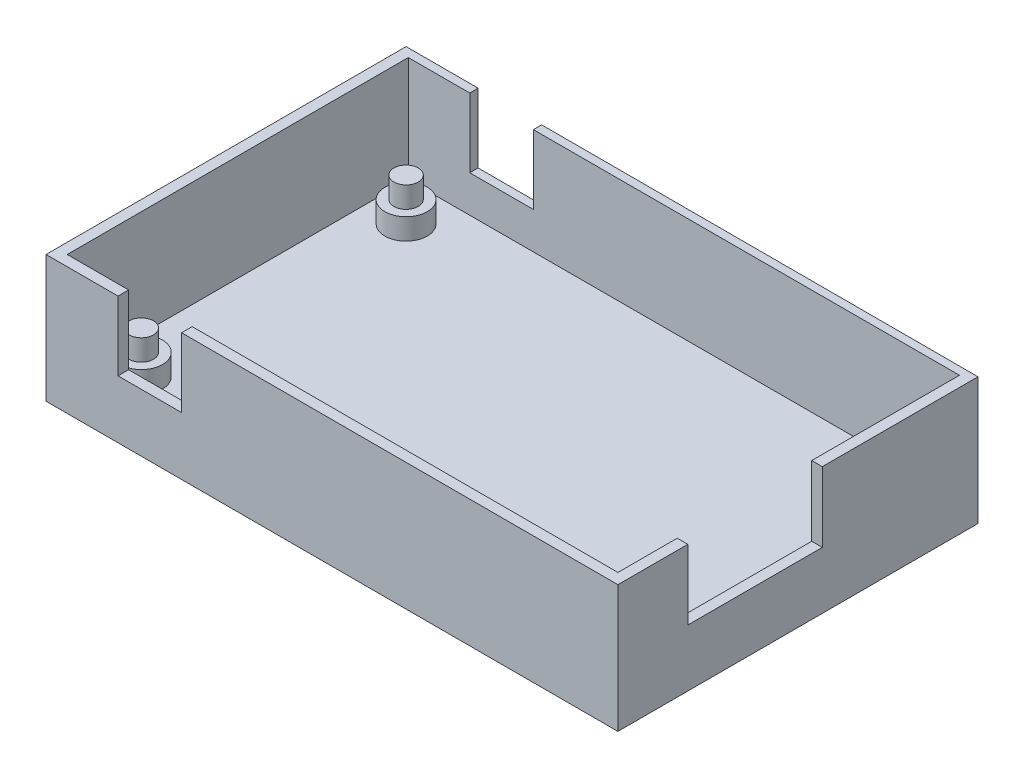
SolidWorks part; units mm, degrees
ref_plane "Front Plane" through (0, 0, 0) normal (0, 0, 1) x (1, 0, 0)
ref_plane "Top Plane" through (0, 0, 0) normal (0, 1, 0) x (1, 0, 0)
ref_plane "Right Plane" through (0, 0, 0) normal (1, 0, 0) x (0, 0, -1)
sketch "Sketch1" plane through (0, 0, 0) normal (0, 1, 0) x (1, 0, 0)
  line L1 (0, 0) -> (68.58, 0)
  line L2 (0, 0) -> (0, 43.18)
  line L3 (0, 43.18) -> (68.58, 43.18)
  line L4 (68.58, 0) -> (68.58, 43.18)
  point P13 (34.29, 43.18)
  point P14 (0, 21.59)
  dimension "D1" = 43.18
  dimension "D2" = 68.58
extrude "Boss-Extrude1" add sketch "Sketch1" along normal blind 2.54
sketch "Sketch5" plane through (0, 2.54, 0) normal (0, 1, 0) x (1, 0, 0)
  line L0 (68.58, 43.18) -> (0, 43.18) construction
  line L1 (68.58, 43.18) -> (0, 43.18) construction
  line L2 (0, 43.18) -> (0, 0) construction
  circle A0 centre (5.715, 37.465) radius 2.54
  circle A1 centre (62.865, 37.465) radius 2.54
  circle A2 centre (5.715, 5.715) radius 2.54
  circle A3 centre (62.865, 5.715) radius 2.54
  point P8 (34.29, 43.18)
  point P11 (34.29, 43.18)
  point P15 (34.29, 43.18)
  point P16 (34.29, 43.18)
  point P17 (0, 21.59)
  point P20 (0, 21.59)
  point P21 (0, 21.59)
  point P22 (0, 21.59)
  dimension "D1" = 5.08
  dimension "D2" = 5.08
  dimension "D3" = 5.08
  dimension "D4" = 5.08
  dimension "D5" = 28.575
  dimension "D6" = 28.575
  dimension "D7" = 28.575
  dimension "D8" = 15.875
  dimension "D9" = 28.575
  dimension "D10" = 15.875
  dimension "D11" = 15.875
  dimension "D12" = 15.875
extrude "Boss-Extrude2" add sketch "Sketch5" along normal blind 2.54
sketch "Sketch6" plane through (0, 2.54, 0) normal (0, 1, 0) x (1, 0, 0)
  line L0 (0, 43.18) -> (0, 0)
  line L1 (0, 0) -> (68.58, 0)
  line L2 (68.58, 0) -> (68.58, 43.18)
  line L3 (68.58, 43.18) -> (0, 43.18)
  line L4 (1.27, 42.1719) -> (1.27, 1.27)
  line L5 (1.27, 1.27) -> (67.31, 1.27)
  line L6 (67.31, 1.27) -> (67.31, 42.2296)
  line L7 (67.31, 42.2296) -> (1.27, 42.1719)
  dimension "D1" = 1.27
  dimension "D2" = 1.27
  dimension "D3" = 1.27
  dimension "D4" = 0.05
extrude "Boss-Extrude3" add sketch "Sketch6" along normal blind 12.7
sketch "Sketch7" plane through (0, 5.08, 0) normal (0, 1, 0) x (1, 0, 0)
  circle A0 centre (5.715, 37.465) radius 1.4605
  circle A1 centre (5.715, 5.715) radius 1.4605
  circle A2 centre (62.865, 5.715) radius 1.4605
  circle A3 centre (62.865, 37.465) radius 1.4605
  dimension "D1" = 2.921
  dimension "D2" = 2.921
  dimension "D3" = 2.921
  dimension "D4" = 2.921
extrude "Boss-Extrude4" add sketch "Sketch7" along normal blind 2.54
sketch "Sketch8" plane through (0, 0, 0) normal (0, 0, 1) x (1, 0, 0)
  line L0 (0, 15.24) -> (68.58, 15.24) construction
  line L1 (8.636, 15.24) -> (16.256, 15.24)
  line L2 (8.636, 15.24) -> (8.636, 6.9544)
  line L3 (8.636, 6.9544) -> (16.256, 6.9544)
  line L4 (16.256, 15.24) -> (16.256, 6.9544)
  line L5 (0, 15.24) -> (0, 0) construction
  dimension "D1" = 8.636
  dimension "D2" = 7.62
  dimension "D3" = 8.2856
extrude "Cut-Extrude1" cut sketch "Sketch8" against normal through all
sketch "Sketch9" plane through (68.58, 0, 0) normal (1, 0, 0) x (0, 0, -1)
  line L0 (0, 15.24) -> (43.18, 15.24) construction
  line L1 (8.382, 15.24) -> (24.511, 15.24)
  line L2 (8.382, 15.24) -> (8.382, 6.858)
  line L3 (8.382, 6.858) -> (24.511, 6.858)
  line L4 (24.511, 15.24) -> (24.511, 6.858)
  line L5 (0, 15.24) -> (0, 0) construction
  dimension "D1" = 24.511
  dimension "D2" = 8.382
  dimension "D3" = 8.382
extrude "Cut-Extrude2" cut sketch "Sketch9" against normal blind 2.032
